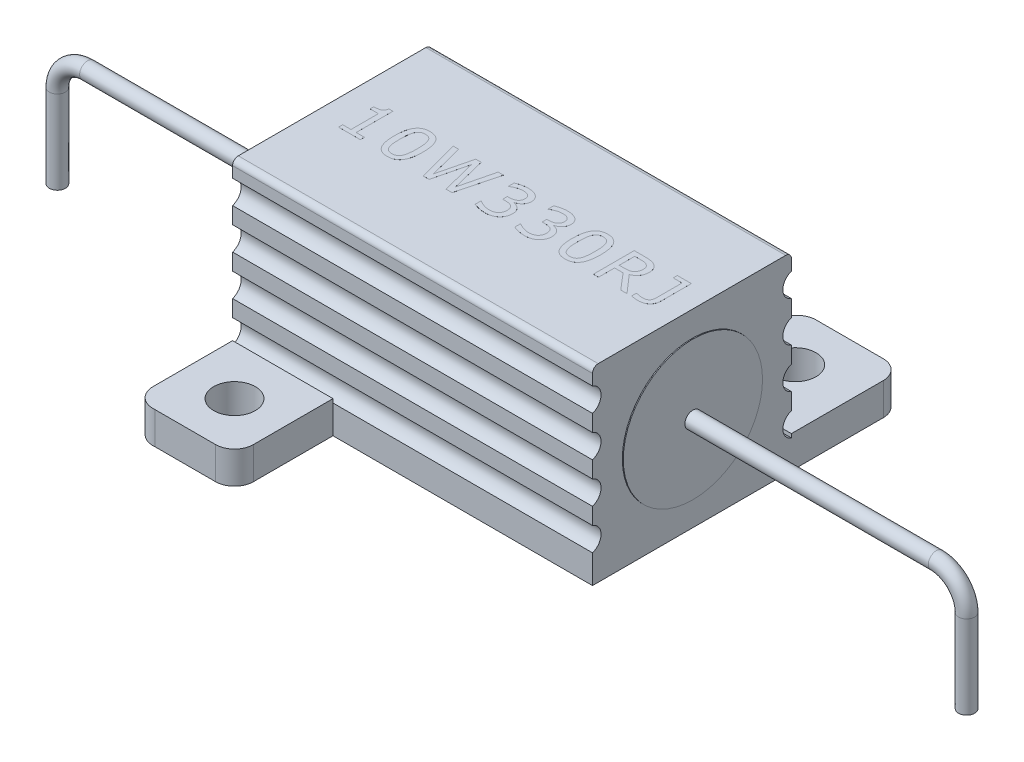
SolidWorks part; units mm, degrees
material "2024-T4"
ref_plane "Front Plane" through (0, 0, 0) normal (0, 0, 1) x (1, 0, 0)
ref_plane "Top Plane" through (0, 0, 0) normal (0, 1, 0) x (1, 0, 0)
ref_plane "Right Plane" through (0, 0, 0) normal (1, 0, 0) x (0, 0, -1)
sketch "Sketch1" plane through (0, 0, 0) normal (1, 0, 0) x (0, 0, -1)
  line L0 (-4.8, 3.5) -> (-4.8, 2.2804) construction
  line L1 (-4.95, 5) -> (4.95, 5)
  line L2 (-5.25, 5) -> (-5.25, -5) construction
  line L3 (-5.25, -5) -> (5.25, -5)
  line L4 (5.25, 4.7) -> (5.25, 4.125)
  line L5 (-5.25, 5) -> (5.25, -5) construction
  line L6 (-5.25, -5) -> (5.25, 5) construction
  line L7 (-5.25, 4.7) -> (-5.25, 4.125)
  line L8 (-5.25, 2.875) -> (-5.25, 2)
  line L9 (-5.25, 0.75) -> (-5.25, -0.125)
  line L10 (-5.25, -1.375) -> (-5.25, -2.25)
  line L11 (-5.25, -3.5) -> (-5.25, -5)
  line L12 (0, 0) -> (0, -1.597) construction
  line L13 (5.25, 4.125) -> (5.25, 2.875) construction
  line L14 (5.25, 2.875) -> (5.25, 2)
  line L15 (5.25, 2) -> (5.25, 0.75) construction
  line L16 (5.25, 0.75) -> (5.25, -0.125)
  line L17 (5.25, -0.125) -> (5.25, -1.375) construction
  line L18 (5.25, -1.375) -> (5.25, -2.25)
  line L19 (5.25, -2.25) -> (5.25, -3.5) construction
  line L20 (5.25, -3.5) -> (5.25, -5)
  arc A0 (-5.25, 4.125) -> (-5.25, 2.875) centre (-5.459, 3.5) cw
  arc A1 (-5.25, 2) -> (-5.25, 0.75) centre (-5.459, 1.375) cw
  arc A2 (-5.25, -0.125) -> (-5.25, -1.375) centre (-5.459, -0.75) cw
  arc A3 (-5.25, -2.25) -> (-5.25, -3.5) centre (-5.459, -2.875) cw
  arc A4 (5.25, -2.25) -> (5.25, -3.5) centre (5.459, -2.875) ccw
  arc A5 (5.25, -0.125) -> (5.25, -1.375) centre (5.459, -0.75) ccw
  arc A6 (5.25, 4.125) -> (5.25, 2.875) centre (5.459, 3.5) ccw
  arc A7 (5.25, 2) -> (5.25, 0.75) centre (5.459, 1.375) ccw
  arc A8 (4.95, 5) -> (5.25, 4.7) centre (4.95, 4.7) cw
  arc A9 (-4.95, 5) -> (-5.25, 4.7) centre (-4.95, 4.7) ccw
  point P0 (0, 0)
  dimension "D3" = 4.8
  dimension "D8" = 0.3
  dimension "D1" = 10
  dimension "D2" = 10.5
  dimension "D4" = 1.5
  dimension "D5" = 1.25
  dimension "D7" = 1.5
  dimension "D6" = 4
extrude "Boss-Extrude1" add sketch "Sketch1" along normal mid plane 19
sketch "Sketch2" plane through (0, -5, 0) normal (0, -1, 0) x (1, 0, 0)
  line L3 (-5.7, 7.85) -> (-5.7, 2.8583) construction
  line L5 (0, 0) -> (13.2167, 0) construction
  line L6 (0, 7.9538) -> (0, -6.2812) construction
  line L15 (9.5, 5.25) -> (9.5, -5.25) construction
  line L16 (-7.2, -11.3006) -> (-7.2, -4.0961) construction
  line L17 (-10.7974, -7.55) -> (-3.5315, -7.55) construction
  line L18 (9.5, -5.25) -> (-9.5, -5.25) construction
  line L19 (-4.2, 9.45) -> (-4.2, 5.25)
  line L20 (-8.4, 10.45) -> (-5.2, 10.45)
  line L21 (-9.5, 5.25) -> (-9.5, 9.455)
  line L22 (-4.2, 5.25) -> (-9.5, 5.25)
  line L23 (4, -9.8) -> (4, -5.25)
  line L24 (4, -5.25) -> (9.5, -5.25)
  line L25 (9.5, -5.25) -> (9.5, -10.1)
  line L26 (8.5, -11.1) -> (5, -11.1)
  line L27 (-6.8, 6.75) -> (2.2661, 6.75) construction
  line L28 (9.5, 5.25) -> (-9.5, 5.25) construction
  line L29 (-9.5, 5.25) -> (-9.5, -5.25) construction
  line L30 (5.35, -8.5) -> (5.35, -9.8) construction
  line L31 (7.55, -8.5) -> (9.5, -8.5) construction
  line L32 (6.45, -9.6) -> (6.45, -11.1) construction
  line L33 (-6.8, 8.95) -> (-6.8, 10.45) construction
  line L34 (6.45, -7.4) -> (11.0136, -7.4) construction
  line L35 (9.5, 5.25) -> (-9.5, 5.25) construction
  circle A9 centre (-6.8, 7.85) radius 1.1
  arc A10 (-4.2, 9.45) -> (-5.2, 10.45) centre (-5.2, 9.45) ccw
  arc A11 (-9.5, 9.455) -> (-8.4, 10.45) centre (-8.5, 9.455) cw
  circle A12 centre (6.45, -8.5) radius 1.1
  arc A13 (9.5, -10.1) -> (8.5, -11.1) centre (8.5, -10.1) cw
  arc A14 (4, -9.8) -> (5, -11.1) centre (4.9536, -10.1011) ccw
  point P13 (4.9, 9.85)
  point P16 (9.5, 9.85)
  point P50 (-4.9, -9.85)
  point P51 (-9.5, -9.85)
  dimension "D3" = 12
  dimension "D4" = 2.2
  dimension "D8" = 1.35
  dimension "D9" = 1.5
  dimension "D1" = 15.2
  dimension "D2" = 4.6
  dimension "D5" = 13.7
  dimension "D6" = 13.5
  dimension "D7" = 2.3
  dimension "D10" = 1.5
  dimension "D11" = 12.65
extrude "Boss-Extrude2" add sketch "Sketch2" against normal blind 1.7
sketch "Sketch3" plane through (0, 0, 0) normal (1, 0, 0) x (0, 0, -1)
  circle A0 centre (0, 0) radius 3.675
  dimension "D1" = 7.35
extrude "Boss-Extrude3" add sketch "Sketch3" along normal mid plane 19.1
sketch "Sketch5" plane through (0, 0, 0) normal (1, 0, 0) x (0, 0, -1)
  circle A0 centre (0, 0) radius 1
  dimension "D1" = 2
extrude "Boss-Extrude4" [suppressed] add sketch "Sketch5" along normal mid plane 48
sketch "Sketch6" [suppressed] plane through (0, 0, 0) normal (0, 0, 1) x (1, 0, 0)
  line L0 (24, -1) -> (24, 1) construction
  line L1 (-15.6066, 0) -> (23.2797, 0) construction
  line L2 (24, 1) -> (24, 5.1151) construction
  line L3 (27.9, 0) -> (27.9, 5.4523) construction
  line L4 (10.6512, 1) -> (24, 1) construction
  line L5 (24, 1) -> (9.55, 1) construction
  line L6 (0, 8.4055) -> (0, -7.6743) construction
  line L7 (24, 1) -> (24, -1)
  arc A0 (24, 1) -> (26.433, 1.85) centre (27.9164, -6.3031) cw
  arc A1 (26.433, 1.85) -> (26.433, -1.85) centre (26, 0) cw
  arc A2 (24, -1) -> (26.433, -1.85) centre (27.9164, 6.3031) ccw
  circle A3 centre (26, 0) radius 1.1649
  dimension "D1" = 3.9
  dimension "D3" = 27.9
  dimension "D2" = 3.7
  dimension "D4" = 2
extrude "Boss-Extrude5" [suppressed] add sketch "Sketch6" along normal mid plane 0.9
mirror "Mirror1" [suppressed] about plane through (0, 0, 0) normal (1, 0, 0)
fillet "Fillet1" [suppressed] radius 1
sketch "Sketch7" plane through (0, 5, 0) normal (0, 1, 0) x (1, 0, 0)
  line L0 (9.5, 0) -> (-9.5, 0) construction
  line L1 (9.5, 4.95) -> (9.5, -4.95) construction
  line L2 (-9.5, 4.95) -> (-9.5, -4.95) construction
  line L3 (9.5, -0.9912) -> (-9.5, -0.9912) construction
  line L4 (9.5, -2.3734) -> (-9.5, -2.3734) construction
  text T0 "10W330RJ\r\n" font "Verdana" height in points 8
extrude "Boss-Extrude6" add sketch "Sketch7" along normal blind 0.001
sketch "Sketch9" plane through (0, 0, 0) normal (0, 0, 1) x (1, 0, 0)
  line L0 (-22.4, 0) -> (22.4, 0)
  line L1 (24, -1.6) -> (24, -6)
  line L2 (0, 0) -> (0, 10.716) construction
  line L3 (-24, -1.6) -> (-24, -6)
  arc A0 (22.4, 0) -> (24, -1.6) centre (22.4, -1.6) cw
  arc A1 (-24, -1.6) -> (-22.4, 0) centre (-22.4, -1.6) cw
  point P4 (0, 0)
  point P11 (24, 0)
  point P14 (-24, 0)
  dimension "D2" = 1.6
  dimension "D1" = 6
  dimension "D3" = 48
sweep "Sweep1" add path "Sketch9" circular profile diameter 0.85 parameters "D3"=0.85
